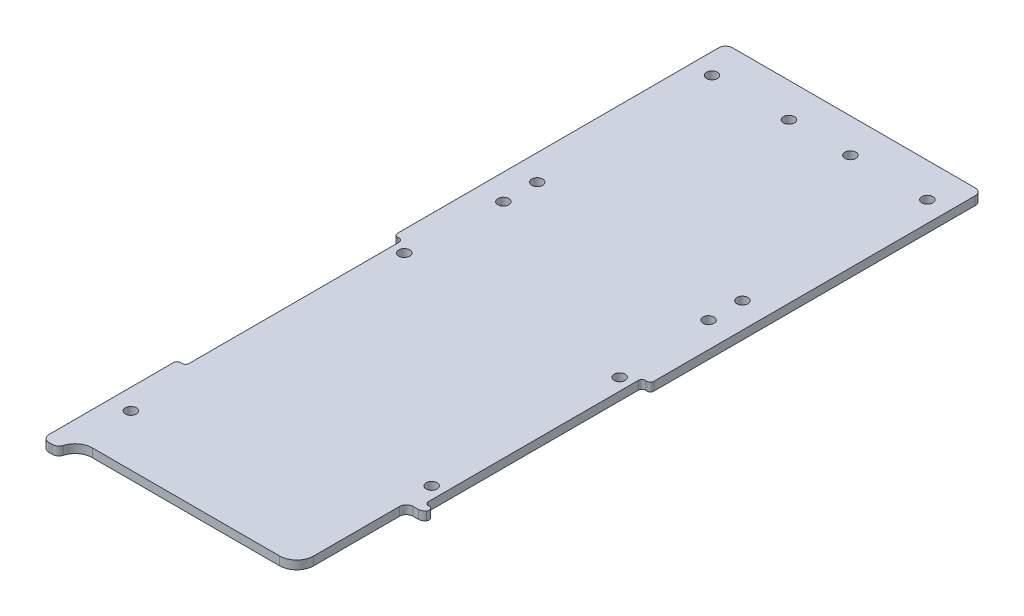
SolidWorks part; units mm, degrees
ref_plane "Front Plane" through (0, 0, 0) normal (0, 0, 1) x (1, 0, 0)
ref_plane "Top Plane" through (0, 0, 0) normal (0, 1, 0) x (1, 0, 0)
ref_plane "Right Plane" through (0, 0, 0) normal (1, 0, 0) x (0, 0, -1)
sketch "Sketch1" plane through (0, 0, 0) normal (0, 1, 0) x (1, 0, 0)
  line L0 (-39.9997, 0) -> (-39.9997, 114.3) construction
  line L1 (-47.625, 127) -> (47.625, 127)
  line L2 (-47.625, 127) -> (-47.625, -127)
  line L3 (-47.625, -127) -> (47.625, -127)
  line L4 (47.625, 127) -> (47.625, -127)
  line L5 (-47.625, 127) -> (47.625, -127) construction
  line L6 (-47.625, -127) -> (47.625, 127) construction
  line L7 (0, 0) -> (0, 127) construction
  line L8 (-39.9997, 0) -> (-39.9997, -101.6) construction
  line L9 (-39.9997, 0) -> (0, 0) construction
  line L10 (-41.275, -127) -> (-41.275, -120.65)
  line L11 (-41.275, -120.65) -> (41.275, -120.65)
  line L12 (41.275, -120.65) -> (41.275, -127)
  line L13 (-39.9997, 114.3) -> (-11.4247, 114.3) construction
  line L14 (39.9997, 114.3) -> (11.4247, 114.3) construction
  circle A0 centre (-39.9997, 114.3) radius 2.032
  circle A1 centre (-39.9997, 0) radius 2.032
  circle A2 centre (-39.9997, -101.6) radius 2.032
  circle A3 centre (39.9997, -101.6) radius 2.032
  circle A4 centre (39.9997, 0) radius 2.032
  circle A5 centre (39.9997, 114.3) radius 2.032
  circle A6 centre (-11.4247, 114.3) radius 2.032
  circle A7 centre (11.4247, 114.3) radius 2.032
  circle A8 centre (-39.9997, -69.85) radius 2.032
  circle A9 centre (39.9997, -69.85) radius 2.032
  point P0 (0, 0)
  dimension "D4" = 4.064
  dimension "D10" = 28.575
  dimension "D1" = 95.25
  dimension "D2" = 254
  dimension "D3" = 7.6253
  dimension "D5" = 12.7
  dimension "D6" = 25.4
  dimension "D7" = 6.35
  dimension "D8" = 6.35
  dimension "D9" = 6.35
  dimension "D11" = 69.85
extrude "Boss-Extrude1" add sketch "Sketch1" along normal blind 3.175 contours L4 L1 L2 L3 A4 A0 A1 A2 A3 A5 | A8 | A3 region at (0, 0, -2.6944) region at (39.9997, 0, 101.6) region at (-39.9997, 0, 69.85)
fillet "Fillet1" radius 2.54 4 edges at (-47.625, 1.5875, -127) (47.625, 1.5875, -127) (47.625, 1.5875, 127) (-47.625, 1.5875, 127)
fillet "Fillet2" radius 2.54 2 edges at (41.275, 1.5875, 127) (-41.275, 1.5875, 127)
fillet "Fillet3" radius 6.35 2 edges at (41.275, 1.5875, 120.65) (-41.275, 1.5875, 120.65)
sketch "Sketch2" plane through (0, 0, 0) normal (0, -1, 0) x (1, 0, 0)
  line L1 (43.815, 127) -> (45.085, 127) construction
  line L2 (40.6451, 123.5787) -> (40.6451, 79.8881)
  line L3 (40.6451, 79.8881) -> (47.625, 79.8881)
  line L11 (47.625, -124.46) -> (47.625, 124.46) construction
  line L12 (43.815, 127) -> (45.085, 127)
  line L13 (47.625, 79.8881) -> (47.625, 124.46)
  arc A0 (35.2956, 120.65) -> (41.3809, 125.1857) centre (35.2956, 127) ccw construction
  arc A1 (43.815, 127) -> (41.3809, 125.1857) centre (43.815, 124.46) ccw construction
  arc A2 (47.625, 124.46) -> (45.085, 127) centre (45.085, 124.46) ccw construction
  arc A3 (40.6451, 123.5787) -> (41.3809, 125.1857) centre (35.2956, 127) ccw
  arc A4 (43.815, 127) -> (41.3809, 125.1857) centre (43.815, 124.46) ccw
  arc A5 (47.625, 124.46) -> (45.085, 127) centre (45.085, 124.46) ccw
  dimension "D2" = 47.1119
  dimension "D1" = 6.9799
extrude "Cut-Extrude1" cut sketch "Sketch2" against normal through all
fillet "Fillet4" radius 6.35 1 edges at (40.6451, 1.5875, 123.5787)
fillet "Fillet5" radius 2.54 2 edges at (47.625, 1.5875, 79.8881) (40.6451, 1.5875, 79.8881)
sketch "Sketch3" plane through (0, 0, 0) normal (0, -1, 0) x (1, 0, 0)
  line L0 (-36.306, -49.7791) -> (-39.9128, -49.7791) construction
  line L1 (-40.4208, -49.276) -> (-40.4208, -45.7043) construction
  line L2 (-35.798, -45.7043) -> (-35.798, -49.276) construction
  line L3 (-39.9128, -45.2013) -> (-36.306, -45.2013) construction
  line L4 (-36.306, -37.2027) -> (-39.9128, -37.2027) construction
  line L5 (-35.798, -33.1279) -> (-35.798, -36.6996) construction
  line L6 (-40.4208, -36.6996) -> (-40.4208, -33.1279) construction
  line L7 (-39.9128, -32.6249) -> (-36.306, -32.6249) construction
  line L8 (36.2872, -32.6249) -> (39.894, -32.6249) construction
  line L9 (40.402, -33.1279) -> (40.402, -36.6996) construction
  line L10 (39.894, -37.2027) -> (36.2872, -37.2027) construction
  line L11 (35.7792, -36.6996) -> (35.7792, -33.1279) construction
  line L12 (36.2872, -45.2013) -> (39.894, -45.2013) construction
  line L13 (35.7792, -49.276) -> (35.7792, -45.7043) construction
  line L14 (40.402, -45.7043) -> (40.402, -49.276) construction
  line L15 (39.894, -49.7791) -> (36.2872, -49.7791) construction
  line L16 (-36.306, -49.7791) -> (-39.9128, -49.7791)
  line L17 (-40.4208, -49.276) -> (-40.4208, -45.7043)
  line L18 (-35.798, -45.7043) -> (-35.798, -49.276)
  line L19 (-39.9128, -45.2013) -> (-36.306, -45.2013)
  line L20 (-36.306, -37.2027) -> (-39.9128, -37.2027)
  line L21 (-35.798, -33.1279) -> (-35.798, -36.6996)
  line L22 (-40.4208, -36.6996) -> (-40.4208, -33.1279)
  line L23 (-39.9128, -32.6249) -> (-36.306, -32.6249)
  line L24 (36.2872, -32.6249) -> (39.894, -32.6249)
  line L25 (40.402, -33.1279) -> (40.402, -36.6996)
  line L26 (39.894, -37.2027) -> (36.2872, -37.2027)
  line L27 (35.7792, -36.6996) -> (35.7792, -33.1279)
  line L28 (36.2872, -45.2013) -> (39.894, -45.2013)
  line L29 (35.7792, -49.276) -> (35.7792, -45.7043)
  line L30 (40.402, -45.7043) -> (40.402, -49.276)
  line L31 (39.894, -49.7791) -> (36.2872, -49.7791)
  line L32 (-47.625, -25.836) -> (47.625, -25.836)
  line L33 (-47.625, -124.46) -> (-47.625, 124.46) construction
  line L34 (47.625, -124.46) -> (47.625, 77.3481) construction
  line L35 (0, -25.836) -> (0, -56.0686) construction
  line L1362 (-40.4208, -34.9138) -> (-35.798, -34.9138)
  line L1857 (-38.1094, -32.6249) -> (-38.1094, -37.2027)
  line L1858 (-38.1094, -45.2013) -> (-38.1094, -49.7791)
  line L1859 (-40.4208, -47.4902) -> (-35.798, -47.4902)
  circle A0 centre (-38.1094, -34.9138) radius 2.032
  circle A1 centre (-38.1094, -47.4902) radius 2.032
  circle A2 centre (38.1094, -47.4902) radius 2.032
  circle A3 centre (38.1094, -34.9138) radius 2.032
  ellipse E0 centre (-39.9128, -45.7043) end of major axis (-39.4048, -45.7043) minor radius 0.5031 (-39.9128, -45.2013) -> (-40.4208, -45.7043) ccw construction
  ellipse E1 centre (-39.9128, -49.276) end of major axis (-39.4048, -49.276) minor radius 0.5031 (-40.4208, -49.276) -> (-39.9128, -49.7791) ccw construction
  ellipse E6 centre (-36.306, -49.276) end of major axis (-35.798, -49.276) minor radius 0.5031 (-36.306, -49.7791) -> (-35.798, -49.276) ccw construction
  ellipse E7 centre (-36.306, -45.7043) end of major axis (-35.798, -45.7043) minor radius 0.5031 (-35.798, -45.7043) -> (-36.306, -45.2013) ccw construction
  ellipse E8 centre (-39.9128, -36.6996) end of major axis (-39.4048, -36.6996) minor radius 0.5031 (-40.4208, -36.6996) -> (-39.9128, -37.2027) ccw construction
  ellipse E9 centre (-36.306, -36.6996) end of major axis (-35.798, -36.6996) minor radius 0.5031 (-36.306, -37.2027) -> (-35.798, -36.6996) ccw construction
  ellipse E10 centre (-36.306, -33.1279) end of major axis (-35.798, -33.1279) minor radius 0.5031 (-35.798, -33.1279) -> (-36.306, -32.6249) ccw construction
  ellipse E11 centre (-39.9128, -33.1279) end of major axis (-39.4048, -33.1279) minor radius 0.5031 (-39.9128, -32.6249) -> (-40.4208, -33.1279) ccw construction
  ellipse E12 centre (39.894, -33.1279) end of major axis (40.402, -33.1279) minor radius 0.5031 (40.402, -33.1279) -> (39.894, -32.6249) ccw construction
  ellipse E13 centre (36.2872, -33.1279) end of major axis (36.7952, -33.1279) minor radius 0.5031 (36.2872, -32.6249) -> (35.7792, -33.1279) ccw construction
  ellipse E14 centre (39.894, -36.6996) end of major axis (40.402, -36.6996) minor radius 0.5031 (39.894, -37.2027) -> (40.402, -36.6996) ccw construction
  ellipse E15 centre (36.2872, -36.6996) end of major axis (36.7952, -36.6996) minor radius 0.5031 (35.7792, -36.6996) -> (36.2872, -37.2027) ccw construction
  ellipse E16 centre (36.2872, -45.7043) end of major axis (36.7952, -45.7043) minor radius 0.5031 (36.2872, -45.2013) -> (35.7792, -45.7043) ccw construction
  ellipse E17 centre (36.2872, -49.276) end of major axis (36.7952, -49.276) minor radius 0.5031 (35.7792, -49.276) -> (36.2872, -49.7791) ccw construction
  ellipse E18 centre (39.894, -45.7043) end of major axis (40.402, -45.7043) minor radius 0.5031 (40.402, -45.7043) -> (39.894, -45.2013) ccw construction
  ellipse E19 centre (39.894, -49.276) end of major axis (40.402, -49.276) minor radius 0.5031 (39.894, -49.7791) -> (40.402, -49.276) ccw construction
  ellipse E20 centre (-39.9128, -45.7043) end of major axis (-39.4048, -45.7043) minor radius 0.5031 (-39.9128, -45.2013) -> (-40.4208, -45.7043) ccw
  ellipse E21 centre (-39.9128, -49.276) end of major axis (-39.4048, -49.276) minor radius 0.5031 (-40.4208, -49.276) -> (-39.9128, -49.7791) ccw
  ellipse E22 centre (-36.306, -49.276) end of major axis (-35.798, -49.276) minor radius 0.5031 (-36.306, -49.7791) -> (-35.798, -49.276) ccw
  ellipse E23 centre (-36.306, -45.7043) end of major axis (-35.798, -45.7043) minor radius 0.5031 (-35.798, -45.7043) -> (-36.306, -45.2013) ccw
  ellipse E24 centre (-39.9128, -36.6996) end of major axis (-39.4048, -36.6996) minor radius 0.5031 (-40.4208, -36.6996) -> (-39.9128, -37.2027) ccw
  ellipse E25 centre (-36.306, -36.6996) end of major axis (-35.798, -36.6996) minor radius 0.5031 (-36.306, -37.2027) -> (-35.798, -36.6996) ccw
  ellipse E26 centre (-36.306, -33.1279) end of major axis (-35.798, -33.1279) minor radius 0.5031 (-35.798, -33.1279) -> (-36.306, -32.6249) ccw
  ellipse E27 centre (-39.9128, -33.1279) end of major axis (-39.4048, -33.1279) minor radius 0.5031 (-39.9128, -32.6249) -> (-40.4208, -33.1279) ccw
  ellipse E28 centre (39.894, -33.1279) end of major axis (40.402, -33.1279) minor radius 0.5031 (40.402, -33.1279) -> (39.894, -32.6249) ccw
  ellipse E29 centre (36.2872, -33.1279) end of major axis (36.7952, -33.1279) minor radius 0.5031 (36.2872, -32.6249) -> (35.7792, -33.1279) ccw
  ellipse E30 centre (39.894, -36.6996) end of major axis (40.402, -36.6996) minor radius 0.5031 (39.894, -37.2027) -> (40.402, -36.6996) ccw
  ellipse E31 centre (36.2872, -36.6996) end of major axis (36.7952, -36.6996) minor radius 0.5031 (35.7792, -36.6996) -> (36.2872, -37.2027) ccw
  ellipse E32 centre (36.2872, -45.7043) end of major axis (36.7952, -45.7043) minor radius 0.5031 (36.2872, -45.2013) -> (35.7792, -45.7043) ccw
  ellipse E33 centre (36.2872, -49.276) end of major axis (36.7952, -49.276) minor radius 0.5031 (35.7792, -49.276) -> (36.2872, -49.7791) ccw
  ellipse E34 centre (39.894, -45.7043) end of major axis (40.402, -45.7043) minor radius 0.5031 (40.402, -45.7043) -> (39.894, -45.2013) ccw
  ellipse E35 centre (39.894, -49.276) end of major axis (40.402, -49.276) minor radius 0.5031 (39.894, -49.7791) -> (40.402, -49.276) ccw
  dimension "D2" = 4.064
extrude "Cut-Extrude2" cut sketch "Sketch3" against normal through all contours A0 | A1 | A2 | A3
sketch "Sketch4" plane through (0, 3.175, 0) normal (0, 1, 0) x (1, 0, 0)
  line L11 (-47.625, 124.46) -> (-47.625, -124.46) construction
  line L12 (-47.625, -76.835) -> (-44.45, -76.835)
  line L13 (-47.625, -76.835) -> (-47.625, 3.81)
  line L15 (-47.625, 3.81) -> (-44.45, 3.81)
  line L16 (-44.45, -76.835) -> (-44.45, 3.81)
  line L17 (47.625, 124.46) -> (47.625, -77.3481) construction
  line L18 (47.625, -76.835) -> (44.45, -76.835)
  line L19 (47.625, -76.835) -> (47.625, 3.81)
  line L20 (47.625, 3.81) -> (44.45, 3.81)
  line L45 (44.45, -76.835) -> (44.45, 3.81)
  line L47 (43.1851, -79.8881) -> (45.085, -79.8881) construction
  dimension "D1" = 3.175
  dimension "D2" = 80.645
  dimension "D3" = 3.0531
extrude "Cut-Extrude3" cut sketch "Sketch4" against normal through all and the other way through all
fillet "Fillet6" radius 1.27 8 edges at (-44.45, 1.5875, -3.81) (-47.625, 1.5875, -3.81) (-47.625, 1.5875, 76.835) (-44.45, 1.5875, 76.835) (44.45, 1.5875, 76.835) (47.625, 1.5875, 76.835) (44.45, 1.5875, -3.81) (47.625, 1.5875, -3.81)
